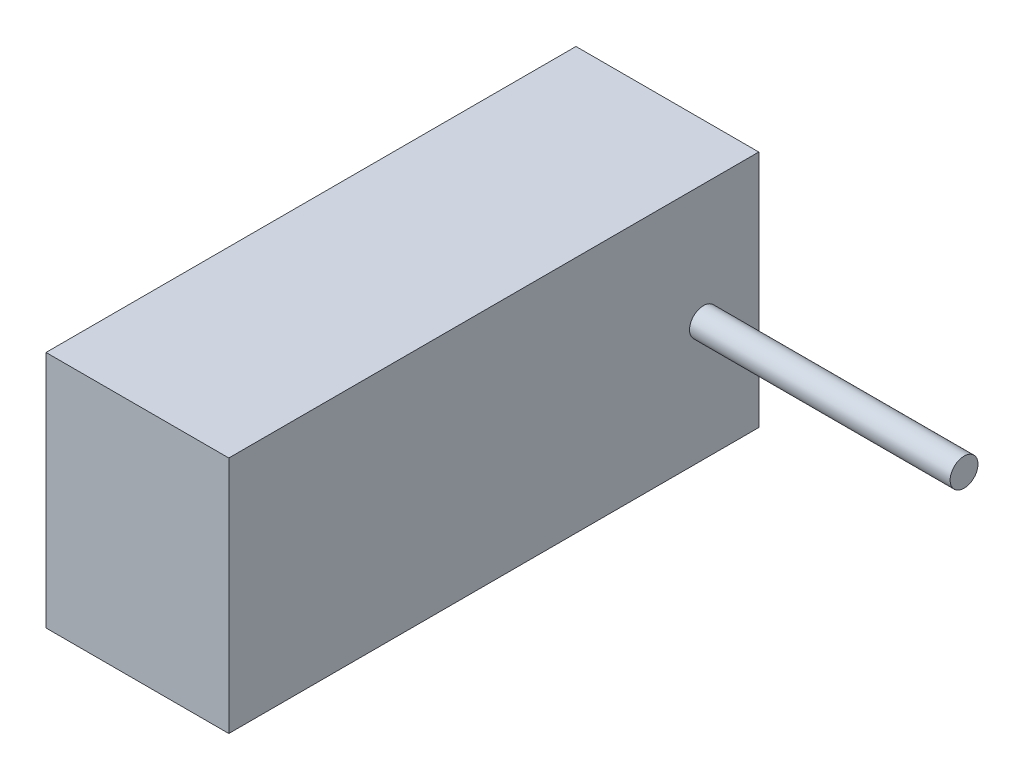
SolidWorks part; units mm, degrees
ref_plane "Plan de face" through (0, 0, 0) normal (0, 0, 1) x (1, 0, 0)
ref_plane "Plan de dessus" through (0, 0, 0) normal (0, 1, 0) x (1, 0, 0)
ref_plane "Plan de droite" through (0, 0, 0) normal (1, 0, 0) x (0, 0, -1)
sketch "Esquisse1" plane through (0, 0, 0) normal (0, 1, 0) x (1, 0, 0)
  line L0 (0, 0) -> (19.15, 0)
  line L1 (0, 0) -> (0, 55.52)
  line L2 (0, 55.52) -> (19.15, 55.52)
  line L3 (19.15, 55.52) -> (19.15, 0)
extrude "Boss.-Extru.1" add sketch "Esquisse1" along normal blind 25 contours L1 L2 L3 L0
sketch "Esquisse3" plane through (0, 0, 0) normal (1, 0, 0) x (0, 0, -1)
  circle A0 centre (49.7267, 12.5) radius 1.46
  point P2 (49.9043, 12.5)
extrude "Boss.-Extru.2" add sketch "Esquisse3" along normal blind 46.45 contours A0
